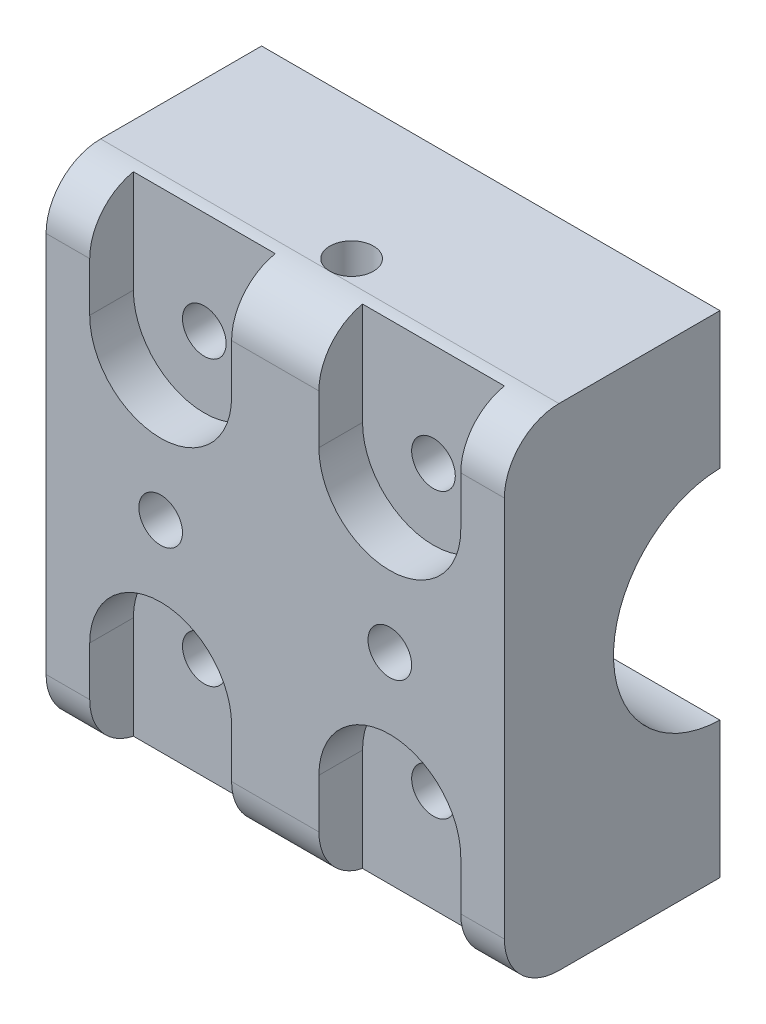
SolidWorks part; units mm, degrees
ref_plane "Front Plane" through (0, 0, 0) normal (0, 0, 1) x (1, 0, 0)
ref_plane "Top Plane" through (0, 0, 0) normal (0, 1, 0) x (1, 0, 0)
ref_plane "Right Plane" through (0, 0, 0) normal (1, 0, 0) x (0, 0, -1)
sketch "Sketch1" plane through (0, 0, 0) normal (1, 0, 0) x (0, 0, -1)
  line L0 (0, 22.5) -> (0, -22.5) construction
  line L1 (-0.25, 22.5) -> (-0.25, 9.9969)
  line L2 (-0.25, -9.9969) -> (-0.25, -22.5)
  line L4 (-0.25, 22.5) -> (-0.25, -22.5) construction
  line L6 (-20, 17.5) -> (-20, -17.5)
  line L8 (0, 22.5) -> (-15, 22.5)
  line L10 (0, 0) -> (-20, 0) construction
  line L12 (0, -22.5) -> (-15, -22.5)
  arc A1 (0, 10) -> (0, -10) centre (0, 0) ccw
  circle A3 centre (0, 0) radius 10 construction
  arc A4 (-15, 22.5) -> (-20, 17.5) centre (-15, 17.5) ccw
  arc A5 (-20, -17.5) -> (-15, -22.5) centre (-15, -17.5) ccw
  point P14 (-20, 0)
  point P18 (-12.7512, 22.6)
  point P23 (-10, 0)
  dimension "D2" = 45
  dimension "D4" = 5
  dimension "D3" = 20
  dimension "D1" = 0.25
extrude "Boss-Extrude1" add sketch "Sketch1" against normal blind 42 contours A1 L1 L2 region at (0, 0, 11.1992)
sketch "Sketch2" plane through (0, 0, 0.25) normal (0, 0, 1) x (1, 0, 0)
  line L0 (0, 0) -> (-42, 0) construction
  line L2 (-42, 13) -> (-21, 13) construction
  line L3 (-10.5, 11) -> (-31.5, 11) construction
  line L4 (-42, 22.5) -> (0, 22.5) construction
  line L5 (-21, 22.5) -> (-21, -22.5) construction
  line L7 (-42, 17.5) -> (-42, -17.5) construction
  line L8 (-42, 17.5) -> (-42, -17.5) construction
  line L9 (-42, -22.5) -> (0, -22.5) construction
  circle A0 centre (-31.5, 13) radius 2
  circle A1 centre (-10.5, 13) radius 2
  circle A2 centre (-10.5, -13) radius 2
  circle A3 centre (-31.5, -13) radius 2
  point P3 (-21, 22.5)
  point P9 (-21, -22.5)
  point P16 (-42, 13)
  point P21 (-21, 11)
  dimension "D2" = 4
  dimension "D1" = 13
extrude "Cut-Extrude2" cut sketch "Sketch2" along normal through all contours A1 | A0 | A3 | A2 region at (-31.5, 13, 0.25) region at (-10.5, 13, 0.25) region at (-10.5, -13, 0.25) region at (-31.5, -13, 0.25)
sketch "Sketch3" plane through (0, 0, 20) normal (0, 0, 1) x (1, 0, 0)
  line L0 (0, 0) -> (-42, 0) construction
  line L1 (-42, 22.5) -> (0, 22.5) construction
  line L2 (-38, 13) -> (-38, 22.5)
  line L3 (-38, 22.5) -> (-25, 22.5)
  line L4 (-25, 22.5) -> (-25, 13)
  line L5 (-17, 13) -> (-17, 22.5)
  line L6 (-17, 22.5) -> (-4, 22.5)
  line L7 (-4, 22.5) -> (-4, 13)
  line L8 (-4, -22.5) -> (-4, -13)
  line L9 (-17, -22.5) -> (-4, -22.5)
  line L10 (-17, -13) -> (-17, -22.5)
  line L11 (-25, -22.5) -> (-25, -13)
  line L12 (-38, -22.5) -> (-25, -22.5)
  line L13 (-38, -13) -> (-38, -22.5)
  line L14 (-42, 17.5) -> (-42, -17.5) construction
  arc A0 (-38, 13) -> (-25, 13) centre (-31.5, 13) ccw
  arc A1 (-17, 13) -> (-4, 13) centre (-10.5, 13) ccw
  arc A2 (-17, -13) -> (-4, -13) centre (-10.5, -13) cw
  arc A3 (-38, -13) -> (-25, -13) centre (-31.5, -13) cw
  dimension "D1" = 13
extrude "Cut-Extrude3" cut sketch "Sketch3" against normal blind 4
sketch "Sketch4" plane through (0, 0, 20) normal (0, 0, 1) x (1, 0, 0)
  circle A0 centre (-10.5, 0) radius 2
  circle A1 centre (-31.5, 0) radius 2
  circle A2 centre (-10.5, 0) radius 2 construction
extrude "Cut-Extrude4" cut sketch "Sketch4" against normal through all
sketch "Sketch5" plane through (0, -22.5, 0) normal (0, -1, 0) x (1, 0, 0)
  line L0 (-21, 20) -> (-21, 0.25) construction
  line L3 (-25, 20) -> (-17, 20) construction
  line L4 (-42, 0.25) -> (0, 0.25) construction
  line L5 (-42, 15) -> (0, 15) construction
  circle A0 centre (-21, 13) radius 2
  point P8 (-21, 11.6588)
  dimension "D1" = 4
extrude "Cut-Extrude5" cut sketch "Sketch5" against normal through all
